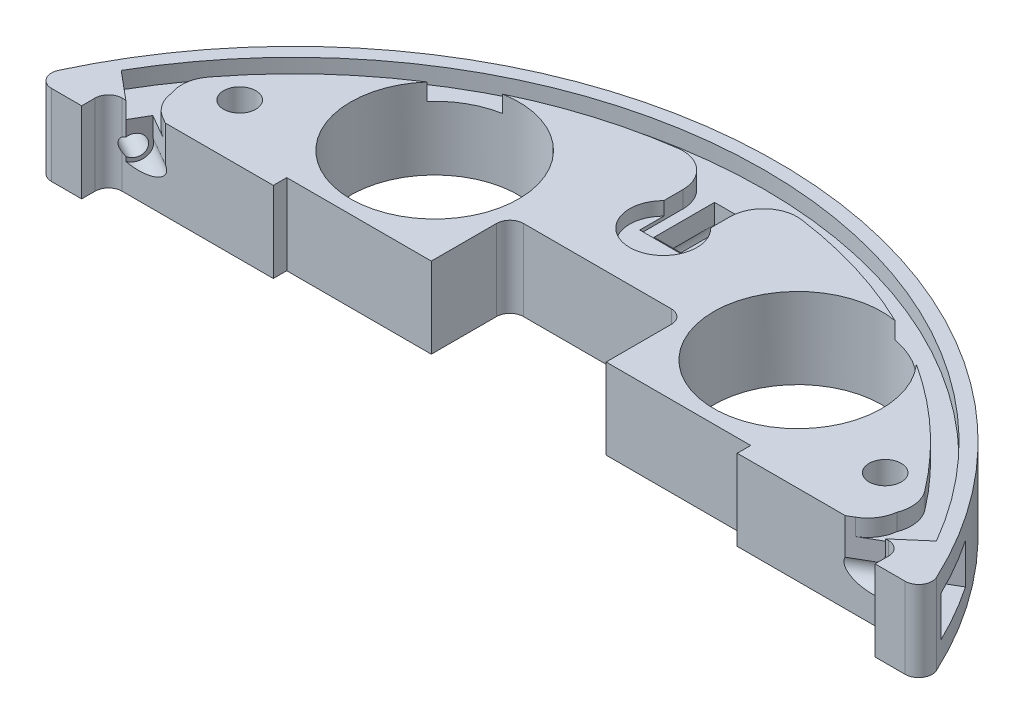
SolidWorks part; units mm, degrees
material "ABS"
ref_plane "Front Plane" through (0, 0, 0) normal (0, 0, 1) x (1, 0, 0)
ref_plane "Top Plane" through (0, 0, 0) normal (0, 1, 0) x (1, 0, 0)
ref_plane "Right Plane" through (0, 0, 0) normal (1, 0, 0) x (0, 0, -1)
sketch "Sketch1" plane through (0, 0, 0) normal (0, 1, 0) x (1, 0, 0)
  line L0 (0, -85) -> (-32.2211, -64.3879) construction
  line L1 (0, -85) -> (0, 0) construction
  arc A0 (36.2245, -62.2237) -> (-36.2245, -62.2237) centre (0, 0) ccw
  arc A1 (29.8119, -61.0352) -> (-29.8119, -61.0352) centre (0, -85) ccw
  arc A2 (36.2245, -62.2237) -> (29.8119, -61.0352) centre (33.7089, -57.9026) cw
  arc A3 (-29.8119, -61.0352) -> (-36.2245, -62.2237) centre (-33.7089, -57.9026) cw
  dimension "D1" = 144
  dimension "D2" = 76.5
  dimension "D4" = 5
  dimension "D3" = 85
extrude "Boss-Extrude1" add sketch "Sketch1" along normal mid plane 12
sketch "solenoid placement" plane through (0, 6, 0) normal (0, 1, 0) x (1, 0, 0)
  line L0 (0, 0) -> (0, -36) construction
  line L5 (-19, -36) -> (19, -36)
  line L7 (19, -36) -> (19, 28)
  line L9 (19, 28) -> (-19, 28)
  line L11 (-19, 28) -> (-19, -36)
  circle A1 centre (0, 0) radius 72 construction
  arc A2 (36.2245, -62.2237) -> (-36.2245, -62.2237) centre (0, 0) ccw construction
  dimension "D1" = 36
  dimension "D2" = 64
  dimension "D3" = 38
extrude "Cut-Extrude1" cut sketch "solenoid placement" against normal through all
sketch "Sketch4" plane through (0, 6, 0) normal (0, 1, 0) x (1, 0, 0)
  line L1 (-13, 28) -> (13, 28)
  line L2 (-13, 28) -> (-13, 43.2)
  line L4 (13, 28) -> (13, 43.2)
  line L5 (11, 45.2) -> (-11, 45.2)
  line L6 (19, 28) -> (-19, 28) construction
  arc A0 (11, 45.2) -> (13, 43.2) centre (11, 43.2) cw
  arc A1 (-11, 45.2) -> (-13, 43.2) centre (-11, 43.2) ccw
  point P6 (0, 28)
  dimension "D1" = 2
  dimension "D2" = 26
  dimension "D3" = 17.2
extrude "Cut-Extrude4" cut sketch "Sketch4" against normal through all
sketch "Sketch5" plane through (0, 6, 0) normal (0, 1, 0) x (1, 0, 0)
  line L0 (0, 0) -> (0, 72) construction
  arc A0 (36.2245, -62.2237) -> (-36.2245, -62.2237) centre (0, 0) ccw construction
  circle A1 centre (27, 48) radius 12.5
  circle A3 centre (-27, 48) radius 12.5
  dimension "D3" = 25
  dimension "D1" = 27
  dimension "D2" = 48
extrude "Cut-Extrude5" cut sketch "Sketch5" against normal through all
sketch "Sketch6" plane through (0, 6, 0) normal (0, 1, 0) x (1, 0, 0)
  line L0 (0, 0) -> (0, 72) construction
  arc A0 (36.2245, -62.2237) -> (-36.2245, -62.2237) centre (0, 0) ccw construction
  circle A1 centre (48, 40) radius 2.4
  circle A6 centre (-48, 40) radius 2.4
  dimension "D3" = 4.8
  dimension "D1" = 48
  dimension "D2" = 40
extrude "Cut-Extrude6" cut sketch "Sketch6" against normal through all
sketch "Sketch3" plane through (0, 6, 0) normal (0, 1, 0) x (1, 0, 0)
  line L1 (-72, -31.5) -> (72, -31.5) construction
  line L2 (-72, -31.5) -> (-72, 27.5)
  line L3 (-59, 31.5) -> (0, 31.5)
  line L4 (72, -31.5) -> (72, 27.5)
  line L5 (0, -31.5) -> (0, 31.5) construction
  line L6 (72, 27.5) -> (59, 27.5)
  line L9 (0, 31.5) -> (59, 31.5)
  line L10 (-72, -31.5) -> (-72, -101.6464)
  line L11 (72, -31.5) -> (72, -101.6464)
  line L12 (72, -101.6464) -> (-72, -101.6464)
  line L13 (59, 27.5) -> (59, 31.5)
  line L14 (-59, 27.5) -> (-59, 31.5)
  line L15 (-72, 27.5) -> (-59, 27.5)
  arc A0 (36.2245, -62.2237) -> (-36.2245, -62.2237) centre (0, 0) ccw construction
  point P0 (0, 0)
  dimension "D2" = 13
  dimension "D1" = 63
  dimension "D3" = 4
extrude "Cut-Extrude3" cut sketch "Sketch3" against normal through all
sketch "Sketch7" plane through (0, 0, 0) normal (0, 1, 0) x (1, 0, 0)
  line L0 (0, 0) -> (62.3538, 36) construction
  line L1 (0, 0) -> (-62.3538, 36) construction
  line L2 (0, 0) -> (0, 72) construction
  arc A0 (0, 72) -> (62.3538, 36) centre (0, 0) cw construction
  arc A1 (0, 72) -> (-62.3538, 36) centre (0, 0) ccw construction
  arc A2 (66.5413, 27.5) -> (-66.5413, 27.5) centre (0, 0) ccw construction
  dimension "D1" = 120
fillet "Fillet1" radius 2 4 edges at (-66.5413, 0, -27.5) (-59, 0, -31.5) (59, 0, -31.5) (66.5413, 0, -27.5)
sketch "Sketch8" plane through (0, 0, 0) normal (0, 1, 0) x (1, 0, 0)
  line L0 (5, 71.8262) -> (5, 68.8262)
  line L1 (0, 0) -> (64.7033, 31.583) construction
  line L2 (64.7033, 31.583) -> (59.7033, 40.2432) construction
  line L3 (64.7033, 31.583) -> (62.1052, 30.083)
  line L4 (62.1052, 30.083) -> (57.1052, 38.7432)
  line L5 (59.7033, 40.2432) -> (57.1052, 38.7432)
  line L6 (0, 0) -> (59.7033, 40.2432) construction
  line L7 (5, 68.8262) -> (-5, 68.8262)
  line L8 (-5, 71.8262) -> (-5, 68.8262)
  line L9 (5, 71.8262) -> (-5, 71.8262) construction
  line L10 (-59.7033, 40.2432) -> (-57.1052, 38.7432)
  line L11 (-57.1052, 38.7432) -> (-62.1052, 30.083)
  line L12 (-64.7033, 31.583) -> (-62.1052, 30.083)
  line L13 (-59.7033, 40.2432) -> (-64.7033, 31.583) construction
  arc A0 (59.7033, 40.2432) -> (64.7033, 31.583) centre (0, 0) cw
  arc A2 (-5, 71.8262) -> (5, 71.8262) centre (0, 0) cw
  arc A3 (-64.7033, 31.583) -> (-59.7033, 40.2432) centre (0, 0) cw
  point P4 (62.3538, 36)
  point P10 (-62.3538, 36)
  point P18 (0, 0)
  dimension "D1" = 10
  dimension "D2" = 3
extrude "Cut-Extrude7" cut sketch "Sketch8" against normal mid plane 6
sketch "Sketch10" plane through (0, 6, 0) normal (0, 1, 0) x (1, 0, 0)
  line L0 (0, 0) -> (0, 55) construction
  circle A0 centre (0, 55) radius 5
  dimension "D2" = 10
  dimension "D1" = 55
extrude "Cut-Extrude9" cut sketch "Sketch10" against normal blind 2
sketch "Sketch11" plane through (0, 6, 0) normal (0, 1, 0) x (1, 0, 0)
  line L1 (34.5, -33.5) -> (-34.5, -33.5)
  line L2 (34.5, -33.5) -> (34.5, 33.5)
  line L3 (34.5, 33.5) -> (-34.5, 33.5)
  line L4 (-34.5, -33.5) -> (-34.5, 33.5)
  line L5 (34.5, -33.5) -> (-34.5, 33.5) construction
  line L6 (34.5, 33.5) -> (-34.5, -33.5) construction
  point P0 (0, 0)
  dimension "D1" = 67
  dimension "D2" = 69
extrude "Cut-Extrude10" cut sketch "Sketch11" against normal through all
sketch "Sketch13" plane through (-59.6052, 0, -34.4131) normal (-0.866, 0, -0.5) x (-0.5, 0, 0.866)
  circle A0 centre (0, 0) radius 1.55
  dimension "D1" = 3.1
extrude "Cut-Extrude11" cut sketch "Sketch13" against normal blind 4.2
sketch "Sketch14" plane through (-55.9679, 0, -32.3131) normal (-0.866, 0, -0.5) x (-0.5, 0, 0.866)
  circle A0 centre (0, 0) radius 2.1
  dimension "D1" = 4.2
extrude "Cut-Extrude12" cut sketch "Sketch14" against normal blind 9
sketch "Sketch15" plane through (-55.9679, 0, -32.3131) normal (0.866, 0, 0.5) x (0.5, 0, -0.866)
  line L1 (-2, 0) -> (2, 0)
  line L2 (-2, 0) -> (-2, 10.8827)
  line L3 (-2, 10.8827) -> (2, 10.8827)
  line L4 (2, 0) -> (2, 10.8827)
  point P0 (0, 0)
  dimension "D1" = 4
extrude "Cut-Extrude13" cut sketch "Sketch15" along normal blind 9
pattern_circular "CirPattern1" count 3 over 120 about axis through (0, 6, 0) along (0, -1, 0) of "Cut-Extrude11", "Cut-Extrude12", "Cut-Extrude13"
sketch "Sketch16" plane through (0, 6, 0) normal (0, 1, 0) x (1, 0, 0)
  line L0 (0, 0) -> (-62.3538, 36) construction
  line L1 (0, 0) -> (62.3538, 36) construction
  line L2 (-56.4374, 31.5) -> (-54.9679, 34.0451) construction
  line L4 (-56.4374, 31.5) -> (-60.6218, 35)
  line L5 (3.5, 55) -> (-3.5, 55)
  line L6 (3.5, 55) -> (3.5, 66.9085)
  line L7 (-53.9374, 35.8301) -> (-55.6706, 37.2799)
  line L8 (-3.5, 55) -> (-3.5, 66.9085)
  line L9 (56.4775, 31.4305) -> (60.6218, 35)
  line L10 (53.9775, 35.7607) -> (55.6964, 37.2412)
  line L12 (54.9679, 34.0451) -> (56.4374, 31.5) construction
  line L13 (-53.9374, 35.8301) -> (-56.4374, 31.5)
  line L14 (53.9775, 35.7607) -> (56.4775, 31.4305)
  arc A0 (60.6218, 35) -> (-60.6218, 35) centre (0, 0) ccw
  arc A1 (55.6964, 37.2412) -> (3.5, 66.9085) centre (0, 0) ccw
  arc A2 (-2, 59.5826) -> (2, 59.5826) centre (0, 55) ccw construction
  arc A3 (-3.5, 66.9085) -> (-55.6706, 37.2799) centre (0, 0) ccw
  arc A4 (59, 29.5) -> (57, 31.5) centre (57, 29.5) ccw construction
  point P6 (0, 0)
  point P15 (0, 55)
  point P26 (54.5534, 34.7631)
  point P27 (57.4922, 31.4385)
  point P33 (0, 0)
  point P34 (0, 0)
  point P35 (-53.1095, 36.0653)
  dimension "D1" = 3
  dimension "D2" = 140
  dimension "D3" = 7
  dimension "D4" = 5
  dimension "D5" = 5
extrude "Cut-Extrude14" cut sketch "Sketch16" against normal blind 2.5
fillet "Fillet2" radius 5 6 edges at (55.6964, 4.75, -37.2412) (-3.5, 4.75, -66.9085) (3.5, 4.75, -66.9085) (-55.6706, 4.75, -37.2799) (54.9679, 4.75, -34.0451) (-54.9679, 4.75, -34.0451)
equation "\"smallPulleyTeeth\"= 30"
equation "\"largePulleyTeeth\"= 30"
equation "\"eighthThick\"= 3.0mm"
equation "\"sixteenthThick\" = 1.7mm"
equation "\"quarterThick\"=6.0mm"
equation "\"OD\" = 145mm"
equation "\"puckAngle\" = 60.5deg"
equation "\"puckDiam\" = 76.5mm"
equation "\"D2@Sketch1\"=\"puckDiam\""
equation "\"D1@Boss-Extrude1\"=\"eighthThick\"*4"
equation "\"axlePress\" = 5.9mm"
equation "\"press\" = 0.2mm"
equation "\"wheelClear\" = 0.3mm"
equation "\"10-32clear\" = 4.8mm"
equation "\"6-32clear\" = 3.3mm"
equation "\"8-32clear\" = 4.0mm"
equation "\"wheelHeight\" = 22mm"
equation "\"wheelWell\" = 65mm"
equation "\"puckDist\" = 85mm"
equation "\"scoopFillet\" = 5mm"
equation "\"4-40clear\" = 3.0mm"
equation "\"D3@Sketch1\"=\"puckDist\""
equation "\"D4@Sketch1\"=\"scoopFillet\""
equation "\"D3@Sketch6\"=\"10-32clear\""
equation "\"D2@Sketch8\"=\"eighthThick\""
equation "\"10-32tap\" = 4.45mm"
equation "\"ledSmall\" = 3.1mm"
equation "\"ledLarge\" = 4.2mm"
equation "\"ledLength\" = 4.2mm"
equation "\"D1@Sketch13\"=\"ledSmall\""
equation "\"D1@Cut-Extrude11\"=\"ledLength\""
equation "\"D1@Sketch14\"=\"ledLarge\""
